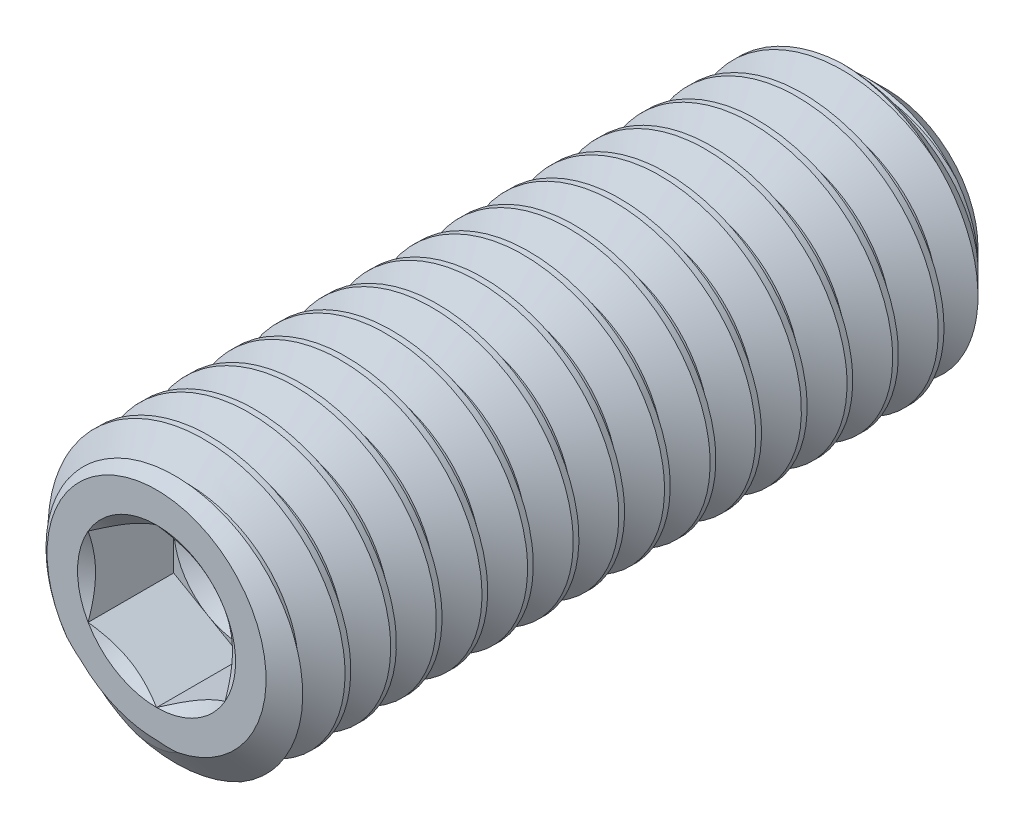
SolidWorks part; units mm, degrees
ref_plane "Front" through (0, 0, 0) normal (0, 0, 1) x (1, 0, 0)
ref_plane "Top" through (0, 0, 0) normal (0, 1, 0) x (1, 0, 0)
ref_plane "Right" through (0, 0, 0) normal (1, 0, 0) x (0, 0, -1)
sketch "Sketch22" plane through (0, 0, 0) normal (1, 0, 0) x (0, 0, -1)
  line L0 (-4, 0) -> (-4, 1.2)
  line L1 (-4, 1.2) -> (-3.7899, 1.5)
  line L2 (-3.7899, 1.5) -> (3.5, 1.5)
  line L3 (3.5, 1.5) -> (4, 1)
  line L4 (-0.145, 1.5) -> (-0.145, -1.5) construction
  line L5 (4, 0) -> (-4, 0)
  line L6 (-4, 1.2) -> (-4, -1.2) construction
  line L7 (4, 0) -> (4, 1)
  point P11 (-0.145, 0)
  dimension "D1" = 2.4
  dimension "Dia" = 3
  dimension "D2" = 0.5
  dimension "Length" = 8
  dimension "D3" = 35
  dimension "D6" = 45
revolve "Revolve1" add sketch "Sketch22" angle 360 about L5
ref_plane "Plane1" through (0, 0, -4) normal (0, 0, 1) x (1, 0, 0)
sketch "Sketch27" plane through (0, 0, -4) normal (0, 0, 1) x (1, 0, 0)
  circle A0 centre (0, 0) radius 1.5 construction
  circle A1 centre (0, 0) radius 1.5
curve "Helix/Spiral1" pitch 0.5 height 8.5 radius 1.5 centre (0, 0, -4) axis (0, 0, 1) start towards (0, 1, 0)
sketch "Sketch28" plane through (0, 0, 0) normal (1, 0, 0) x (0, 0, -1)
  line L0 (4, 1.5) -> (4.4375, 1.5)
  line L1 (4.4375, 1.5) -> (4.25, 1.1752)
  line L2 (4.25, 1.1752) -> (4.1875, 1.1752)
  line L3 (4.1875, 1.1752) -> (4, 1.5)
  line L4 (4.0937, 1.3376) -> (4.3437, 1.3376) construction
  line L6 (-3.7899, 1.5) -> (3.5, 1.5) construction
  dimension "D1" = 0.0625
  dimension "D2" = 0.25
  dimension "D3" = 60
sweep "Cut-Sweep2" cut profiles "Sketch28" path "Helix/Spiral1" align with end faces yes
sketch "Sketch23" plane through (0, 0, 4) normal (0, 0, 1) x (1, 0, 0)
  line L1 (0, 0.866) -> (-0.75, 0.433)
  line L2 (-0.75, 0.433) -> (-0.75, -0.433)
  line L3 (-0.75, -0.433) -> (0, -0.866)
  line L4 (0, -0.866) -> (0.75, -0.433)
  line L5 (0.75, -0.433) -> (0.75, 0.433)
  line L6 (0.75, 0.433) -> (0, 0.866)
  circle A0 centre (0, 0) radius 0.75 construction
  dimension "Hex" = 1.5
extrude "Cut-Extrude10" cut sketch "Sketch23" against normal blind 0.9375
sketch "Sketch24" plane through (0, 0, 4) normal (0, 0, 1) x (1, 0, 0)
  circle A0 centre (0, 0) radius 0.866
extrude "Cut-Extrude11" cut sketch "Sketch24" against normal through all draft 55
sketch "Sketch26" plane through (0, 0, 3.0625) normal (0, 0, 1) x (1, 0, 0)
  circle A0 centre (0, 0) radius 0.75 construction
  circle A1 centre (0, 0) radius 0.75
extrude "Cut-Extrude12" cut sketch "Sketch26" against normal through all draft 60
sketch "Sketch30" plane through (0, 0, 0) normal (1, 0, 0) x (0, 0, -1)
  line L0 (-3.7899, 1.5) -> (3.5, 1.5) construction
  line L1 (-4, 0) -> (-4, 1.2) construction
  line L2 (4, 0) -> (4, 1) construction
  point P0 (-4, 1.5)
  point P1 (4, 1.5)
  point P2 (4, -1.5)
  point P11 (2.75, -1.5)
  dimension "D1" = 1.25
equation "\"D1@Sketch28\" = \"D4@Helix/Spiral1\" * .125"
equation "\"D2@Sketch28\" = \"D4@Helix/Spiral1\" * .5"
equation "\"D3@Helix/Spiral1\" = \"Length@Sketch22\" + \"D4@Helix/Spiral1\""
equation "\"D1@Sketch30\" = \"D4@Helix/Spiral1\" * 2.5"
equation "\"hex Depth@Cut-Extrude10\" = \"Hex@Sketch23\" * .625"
equation "\"D1@Sketch22\" = \"Dia@Sketch22\" * .8"
equation "\"D2@Sketch22\" = \"D4@Helix/Spiral1\""
